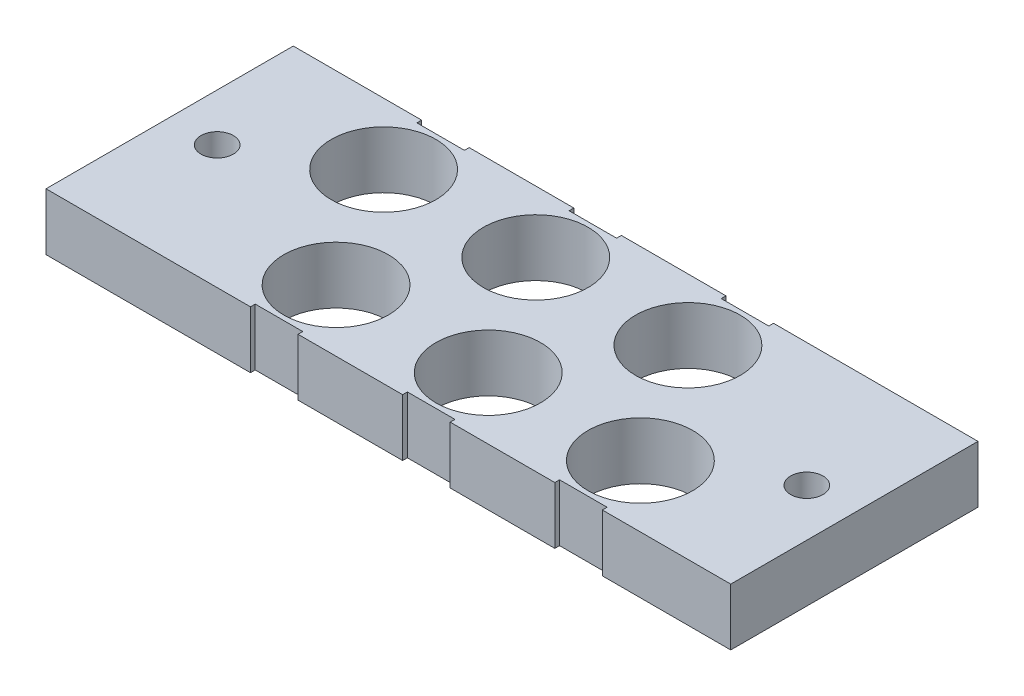
SolidWorks part; units mm, degrees
ref_plane "Front Plane" through (0, 0, 0) normal (0, 0, 1) x (1, 0, 0)
ref_plane "Top Plane" through (0, 0, 0) normal (0, 1, 0) x (1, 0, 0)
ref_plane "Right Plane" through (0, 0, 0) normal (1, 0, 0) x (0, 0, -1)
sketch "Sketch1" plane through (0, 0, 0) normal (0, 1, 0) x (1, 0, 0)
  line L0 (3.1864, -4.1649) -> (6.1864, -4.1649)
  line L1 (19.1864, -4.1649) -> (22.1864, -4.1649)
  line L2 (27.1864, -30.1649) -> (30.1864, -30.1649)
  line L3 (11.1864, -30.1649) -> (14.1864, -30.1649)
  line L4 (43.1864, -30.1649) -> (52.6864, -30.1649)
  line L5 (52.6864, -30.1649) -> (52.6864, -4.1649)
  line L6 (52.6864, -4.1649) -> (35.1864, -4.1649)
  line L7 (-9.8136, -4.1649) -> (-19.3136, -4.1649)
  line L8 (-19.3136, -4.1649) -> (-19.3136, -30.1649)
  line L9 (-19.3136, -30.1649) -> (-1.8136, -30.1649)
  line L10 (-14.3136, -4.1649) -> (-14.3136, -30.1649) construction
  line L11 (47.6864, -4.1649) -> (47.6864, -30.1649) construction
  circle A0 centre (-14.3136, -17.1649) radius 1.7
  circle A1 centre (47.6864, -17.1649) radius 1.7
  line B0 (35.1864, -17.1649) -> (35.1864, -4.1649)
  line B1 (11.1864, -30.1649) -> (7.1864, -30.1649)
  line B2 (-1.3136, -29.6649) -> (10.6864, -29.6649)
  line B3 (11.1864, -30.1649) -> (11.1864, -17.1649)
  line B4 (27.1864, -30.1649) -> (27.1864, -17.1649)
  line B5 (43.1864, -30.1649) -> (43.1864, -17.1649)
  line B6 (-1.8136, -17.1649) -> (-1.8136, -30.1649)
  line B7 (10.6864, -29.6649) -> (10.6864, -17.6649)
  line B8 (30.1864, -17.1649) -> (30.1864, -30.1649)
  line B9 (22.1864, -4.1649) -> (22.1864, -17.1649)
  line B10 (34.6864, -16.6649) -> (34.6864, -4.6649)
  line B11 (18.6864, -16.6649) -> (18.6864, -4.6649)
  line B12 (3.1864, -17.1649) -> (3.1864, -4.1649)
  line B13 (42.6864, -29.6649) -> (42.6864, -17.6649)
  line B14 (14.6864, -29.6649) -> (26.6864, -29.6649)
  line B15 (30.6864, -17.6649) -> (30.6864, -29.6649)
  line B16 (30.6864, -17.6649) -> (42.6864, -29.6649) construction
  line B17 (14.6864, -17.6649) -> (26.6864, -29.6649) construction
  line B18 (-1.3136, -17.6649) -> (10.6864, -29.6649) construction
  line B19 (43.1864, -17.1649) -> (30.1864, -17.1649)
  line B20 (2.6864, -16.6649) -> (2.6864, -4.6649)
  line B21 (14.6864, -17.6649) -> (14.6864, -29.6649)
  line B22 (27.1864, -30.1649) -> (23.1864, -30.1649)
  line B23 (30.1864, -30.1649) -> (34.1864, -30.1649)
  line B24 (43.1864, -30.1649) -> (39.1864, -30.1649)
  line B25 (-9.3136, -10.6649) -> (2.6864, -10.6649) construction
  line B26 (6.6864, -10.6649) -> (18.6864, -10.6649) construction
  line B27 (22.6864, -10.6649) -> (34.6864, -10.6649) construction
  line B28 (-1.3136, -23.6649) -> (10.6864, -23.6649) construction
  line B29 (14.6864, -23.6649) -> (26.6864, -23.6649) construction
  line B30 (30.6864, -23.6649) -> (42.6864, -23.6649) construction
  line B31 (-27.4152, -23.6649) -> (51.2342, -23.6649) construction
  line B32 (22.1864, -17.1649) -> (35.1864, -17.1649)
  line B33 (-27.4152, -10.6649) -> (51.2342, -10.6649) construction
  line B34 (28.6864, -16.6649) -> (28.6864, -4.6649) construction
  line B35 (36.6864, -17.6649) -> (36.6864, -29.6649) construction
  line B36 (20.6864, -17.6649) -> (20.6864, -29.6649) construction
  line B37 (12.6864, -16.6649) -> (12.6864, -4.6649) construction
  line B38 (4.6864, -17.6649) -> (4.6864, -29.6649) construction
  line B39 (-3.3136, -16.6649) -> (-3.3136, -4.6649) construction
  line B40 (22.6864, -4.6649) -> (22.6864, -16.6649)
  line B41 (22.6864, -16.6649) -> (34.6864, -16.6649)
  line B42 (34.6864, -4.6649) -> (22.6864, -4.6649)
  line B43 (34.6864, -16.6649) -> (22.6864, -4.6649) construction
  line B44 (34.6864, -4.6649) -> (22.6864, -16.6649) construction
  line B45 (35.1864, -4.1649) -> (31.1864, -4.1649)
  line B46 (22.1864, -4.1649) -> (26.1864, -4.1649)
  line B47 (31.1864, -4.1649) -> (31.1864, -4.6649)
  line B48 (26.1864, -4.1649) -> (26.1864, -4.6649)
  circle B49 centre (28.6864, -10.6649) radius 5.5
  line B50 (-1.3136, -17.6649) -> (-1.3136, -29.6649)
  line B51 (10.6864, -17.6649) -> (-1.3136, -17.6649)
  line B52 (-1.3136, -29.6649) -> (10.6864, -17.6649) construction
  line B53 (11.1864, -17.1649) -> (-1.8136, -17.1649)
  line B54 (-1.8136, -30.1649) -> (2.1864, -30.1649)
  line B55 (2.1864, -30.1649) -> (2.1864, -29.6649)
  line B56 (7.1864, -30.1649) -> (7.1864, -29.6649)
  circle B57 centre (4.6864, -23.6649) radius 5.5
  line B58 (26.6864, -29.6649) -> (26.6864, -17.6649)
  line B59 (26.6864, -17.6649) -> (14.6864, -17.6649)
  line B60 (14.6864, -29.6649) -> (26.6864, -17.6649) construction
  line B61 (27.1864, -17.1649) -> (14.1864, -17.1649)
  line B62 (14.1864, -17.1649) -> (14.1864, -30.1649)
  line B63 (14.1864, -30.1649) -> (18.1864, -30.1649)
  line B64 (18.1864, -30.1649) -> (18.1864, -29.6649)
  line B65 (23.1864, -30.1649) -> (23.1864, -29.6649)
  circle B66 centre (20.6864, -23.6649) radius 5.5
  line B67 (42.6864, -17.6649) -> (30.6864, -17.6649)
  line B68 (30.6864, -29.6649) -> (42.6864, -29.6649)
  line B69 (30.6864, -29.6649) -> (42.6864, -17.6649) construction
  line B70 (34.1864, -30.1649) -> (34.1864, -29.6649)
  line B71 (39.1864, -30.1649) -> (39.1864, -29.6649)
  circle B72 centre (36.6864, -23.6649) radius 5.5
  line B73 (6.6864, -4.6649) -> (6.6864, -16.6649)
  line B74 (6.6864, -16.6649) -> (18.6864, -16.6649)
  line B75 (18.6864, -4.6649) -> (6.6864, -4.6649)
  line B76 (18.6864, -16.6649) -> (6.6864, -4.6649) construction
  line B77 (18.6864, -4.6649) -> (6.6864, -16.6649) construction
  line B78 (6.1864, -17.1649) -> (19.1864, -17.1649)
  line B79 (19.1864, -17.1649) -> (19.1864, -4.1649)
  line B80 (6.1864, -4.1649) -> (6.1864, -17.1649)
  line B81 (19.1864, -4.1649) -> (15.1864, -4.1649)
  line B82 (6.1864, -4.1649) -> (10.1864, -4.1649)
  line B83 (15.1864, -4.1649) -> (15.1864, -4.6649)
  line B84 (10.1864, -4.1649) -> (10.1864, -4.6649)
  circle B85 centre (12.6864, -10.6649) radius 5.5
  line B86 (-9.3136, -4.6649) -> (-9.3136, -16.6649)
  line B87 (-9.3136, -16.6649) -> (2.6864, -16.6649)
  line B88 (2.6864, -4.6649) -> (-9.3136, -4.6649)
  line B89 (2.6864, -16.6649) -> (-9.3136, -4.6649) construction
  line B90 (2.6864, -4.6649) -> (-9.3136, -16.6649) construction
  line B91 (-9.8136, -17.1649) -> (3.1864, -17.1649)
  line B92 (-9.8136, -4.1649) -> (-9.8136, -17.1649)
  line B93 (3.1864, -4.1649) -> (-0.8136, -4.1649)
  line B94 (-9.8136, -4.1649) -> (-5.8136, -4.1649)
  line B95 (-0.8136, -4.1649) -> (-0.8136, -4.6649)
  line B96 (-5.8136, -4.1649) -> (-5.8136, -4.6649)
  circle B97 centre (-3.3136, -10.6649) radius 5.5
  dimension "D1" = 9.5
  dimension "D2" = 9.5
  dimension "D3" = 72
  dimension "D4" = 5
  dimension "D5" = 5
sketch_block_instance "Block1-5"
sketch_block "Block1" parameters "D3"=6, "D1"=12, "D2"=12, "D4"=12, "D5"=78.6494, "D6"=78.6494, "D7"=78.6494, "D8"=10.3235, "D9"=14.0261, "D10"=17.7654, "D11"=23.7534, "D12"=22.7743, "D13"=52
sketch_block_instance "Block2-2"
sketch_block "Block2" parameters "D2"=8, "D1"=12
sketch_block_instance "Block2-3"
sketch_block_instance "Block2-4"
sketch_block_instance "Block2-5"
sketch_block_instance "Block2-6"
sketch_block_instance "Block2-7"
sketch_block_instance "Block3-1"
sketch_block "Block3"
sketch_block_instance "Block4-1"
sketch_block "Block4"
sketch_block_instance "Block5-1"
sketch_block "Block5"
sketch_block_instance "Block6-1"
sketch_block "Block6"
sketch_block_instance "Block7-1"
sketch_block "Block7"
sketch_block_instance "Block8-1"
sketch_block "Block8"
extrude "Boss-Extrude1" add sketch "Sketch1" against normal blind 6 contours B20 B88 B86 B87 B97 | B11 B75 B73 B74 B85 | B10 B42 B40 B41 B49 | B21 B14 B58 B59 B66 | B50 B2 B7 B51 B57 | B15 B68 B13 B67 B72 region at (0.9364, 0, 4.8346) region at (12.6864, 0, 4.8346) region at (0.4364, 0, 29.4952) region at (16.4364, 0, 29.4952) region at (28.6864, 0, 4.8346) region at (32.4364, 0, 29.4952)
extrude "Boss-Extrude2" add sketch "Sketch1<3>" against normal blind 6 contours B5 L4 L5 L6 B0 B19 A1 | B92 L7 L8 L9 B6 B91 A0 | B12 B53 B80 L0 | B78 B3 L3 B62 | B8 B32 B4 L2 | B71 B24 B5 B19 B32 B8 B23 B70 B68 B15 B67 B13 | B65 B22 B4 B32 B61 B62 B63 B64 B14 B21 B59 B58 | B96 B94 B92 B91 B53 B12 B93 B95 B88 B20 B87 B86 | B84 B82 B80 B53 B78 B61 B79 B81 B83 B75 B11 B74 B73 | B79 B61 B9 L1 | B48 B46 B9 B32 B0 B45 B47 B42 B10 B41 B40 | B56 B1 B3 B53 B6 B54 B55 B2 B50 B51 B7 region at (4.6864, 0, 10.6649) region at (3.0025, 0, 10.6649) region at (8.1864, 0, 4.3487) region at (4.6864, 0, 17.3487) region at (-11.9088, 0, 19.1419) region at (12.6864, 0, 23.6649) region at (16.6864, 0, 17.3487) region at (20.6864, 0, 10.6649) region at (22.3702, 0, 10.6649) region at (28.6864, 0, 23.6649) region at (32.6864, 0, 17.3487) region at (45.2816, 0, 15.1878)
sketch "Sketch1<3>" plane through (0, 0, 0) normal (0, 1, 0) x (1, 0, 0) same geometry as "Sketch1"
sketch "Sketch2" plane through (0, -6, 0) normal (0, -1, 0) x (-1, 0, 0)
  text T0 "F6"
extrude "Cut-Extrude1" cut sketch "Sketch2" against normal blind 1
